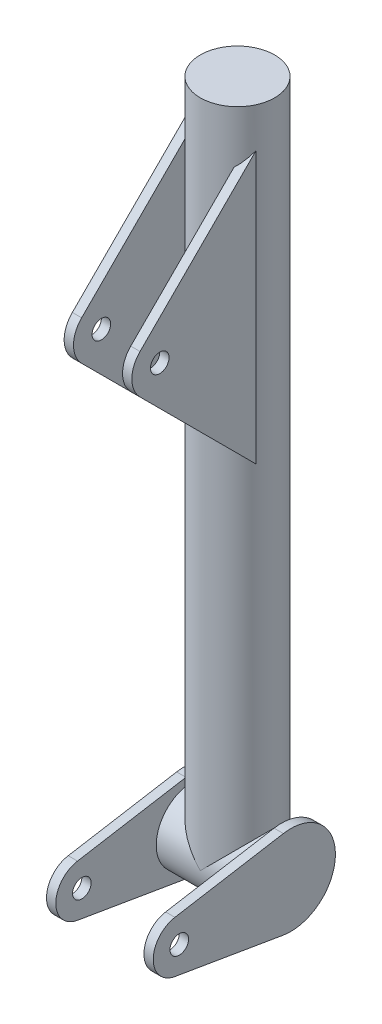
SolidWorks part; units mm, degrees
ref_plane "Front Plane" through (0, 0, 0) normal (1, 0, 0) x (0, 1, 0)
ref_plane "Top Plane" through (0, 0, 0) normal (0, 0, 1) x (0, 1, 0)
ref_plane "Right Plane" through (0, 0, 0) normal (0, 1, 0) x (-1, 0, 0)
sketch "Sketch1" plane through (0, 0, 0) normal (1, 0, 0) x (0, 1, 0)
  line L0 (-8.7657, 39.5817) -> (-15.0268, 2.54)
  line L1 (8.7657, 39.5817) -> (15.0268, 2.54)
  line L2 (161.9462, 44.8352) -> (117.111, 0)
  line L3 (117.111, 0) -> (220.2518, 0)
  line L4 (220.2518, 0) -> (175.4166, 44.8352)
  line L5 (168.6814, 38.1) -> (168.6814, 0) construction
  arc A0 (-15.0268, 2.54) -> (15.0268, 2.54) centre (0, 0) ccw
  circle A1 centre (0, 38.1) radius 3.175
  arc A2 (8.7657, 39.5817) -> (-8.7657, 39.5817) centre (0, 38.1) ccw
  circle A3 centre (0, 0) radius 12.7
  arc A4 (175.4166, 44.8352) -> (161.9462, 44.8352) centre (168.6814, 38.1) ccw
  circle A5 centre (168.6814, 38.1) radius 3.175
  dimension "D1" = 30.48
  dimension "D2" = 6.35
  dimension "D3" = 17.78
  dimension "D5" = 25.4
  dimension "D7" = 19.05
  dimension "D4" = 38.1
  dimension "D6" = 168.6814
extrude "Boss-Extrude1" add sketch "Sketch1" along normal mid plane 30.099 contours A3
extrude "Boss-Extrude2" add sketch "Sketch1<6>" along normal blind 3.175 from surface contours L1 A2 L0 A0 A3 A1 | A3 region at (0, 0, 20.2102) region at (0, 0, 0) starting at face at (15.0495, 0, -12.7)
sketch "Sketch1<6>" plane through (0, 0, 0) normal (1, 0, 0) x (0, 1, 0) same geometry as "Sketch1"
extrude "Boss-Extrude3" add sketch "Sketch1<8>" along normal blind 3.175 from offset 8.382 separate body contours A5 L3 L4 A4 L2 region at (0, 168.6814, 16.7021)
sketch "Sketch1<8>" plane through (0, 0, 0) normal (1, 0, 0) x (0, 1, 0) same geometry as "Sketch1"
sketch "Sketch2" plane through (0, 0, 0) normal (0, 1, 0) x (-1, 0, 0)
  circle A0 centre (0, 0) radius 12.7
  dimension "D1" = 25.4
extrude "Boss-Extrude4" add sketch "Sketch2" along normal blind 228.6 contours A0
mirror "Mirror1" about plane through (0, 0, 0) normal (1, 0, 0) of bodies 104
